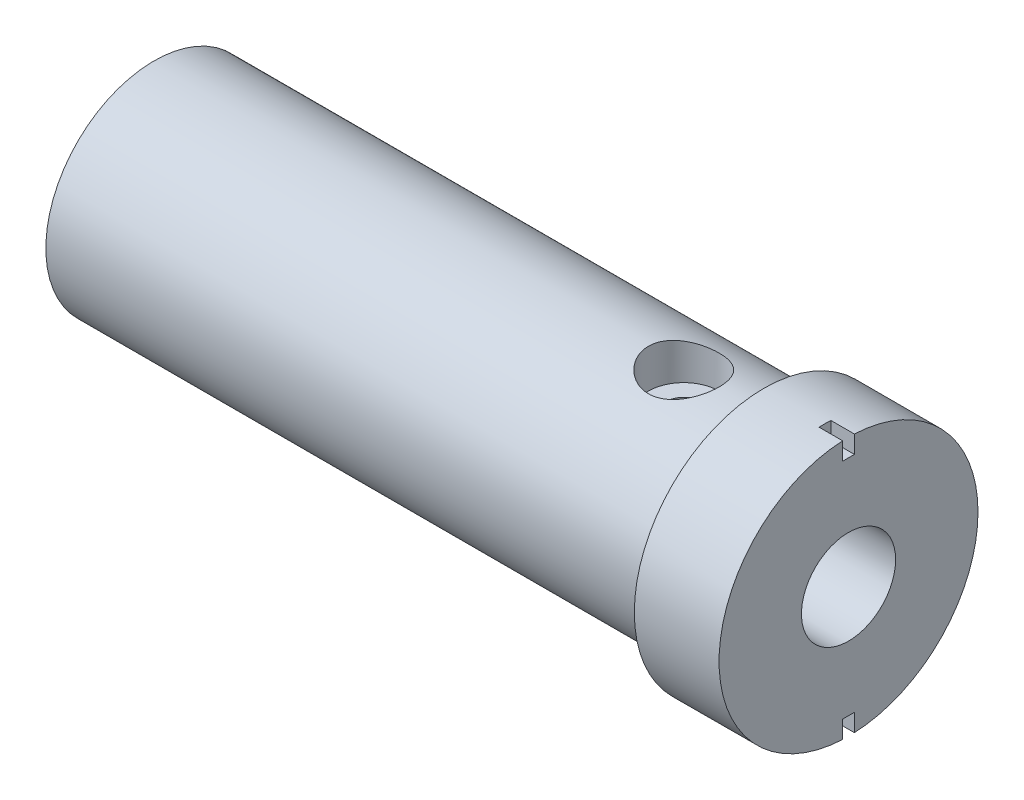
SolidWorks part; units mm, degrees
material "1060 Alloy"
ref_plane "Front Plane" through (0, 0, 0) normal (0, 0, 1) x (1, 0, 0)
ref_plane "Top Plane" through (0, 0, 0) normal (0, 1, 0) x (1, 0, 0)
ref_plane "Right Plane" through (0, 0, 0) normal (1, 0, 0) x (0, 0, -1)
ref_plane "Plane2" through (0, 3.1, 0) normal (0, 1, 0) x (1, 0, 0)
sketch "Sketch1" plane through (0, 0, 0) normal (0, 1, 0) x (1, 0, 0)
  line L0 (0, 0) -> (-90.15, 0) construction
  line L1 (0, 0) -> (0, 11)
  line L2 (0, 11) -> (-7.2, 11)
  line L3 (-7.2, 11) -> (-7.2, 9.2)
  line L4 (-7.2, 9.2) -> (-59, 9.2)
  line L5 (-59, 9.2) -> (-59, 0)
  line L6 (0, 0) -> (-59, 0)
  dimension "D1" = 7.2
  dimension "D2" = 59
  dimension "D3" = 11
  dimension "D4" = 9.2
revolve "Revolve1" add sketch "Sketch1" angle 360 about L0
sketch "Sketch2" plane through (0, 0, 0) normal (1, 0, 0) x (0, 0, -1)
  line L0 (-2.5278, 3.1) -> (2.5278, 3.1)
  line L1 (0.5, 10.9886) -> (0.5, 9.4886)
  line L2 (0.5, 9.4886) -> (-0.5, 9.4886)
  line L3 (-0.5, 9.4886) -> (-0.5, 10.9886)
  line L4 (0, 0) -> (4, 0) construction
  line L5 (-0.5, -9.4886) -> (-0.5, -10.9886)
  line L6 (0.5, -9.4886) -> (-0.5, -9.4886)
  line L7 (0.5, -10.9886) -> (0.5, -9.4886)
  circle A0 centre (0, 0) radius 4
  circle A1 centre (0, 0) radius 11 construction
  circle A2 centre (0, 0) radius 11
  circle M3 centre (0, 0) radius 11
  dimension "D1" = 8
  dimension "D2" = 3.1
  dimension "D3" = 0.5
  dimension "D4" = 1
  dimension "D5" = 1.5
extrude "Cut-Extrude1" cut sketch "Sketch2" against normal blind 20 contours L0 A0 | L0 A0 region at (0, 3.4637, 0) region at (0, -0.2284, 0)
sketch "Sketch3" plane through (0, 3.1, 0) normal (0, 1, 0) x (-1, 0, 0)
  line L0 (0, 0) -> (14, 0) construction
  circle A1 centre (14, 0) radius 1.475
  circle A2 centre (14, 0) radius 3
  point P5 (-14, 0)
  point P6 (-14, 0)
  point P7 (-14, 0)
  point P8 (14, 0)
  dimension "D2" = 2.95
  dimension "D3" = 6
  dimension "D1" = 14
extrude "Cut-Extrude3" cut sketch "Sketch3" along normal through all contours A1 region at (-14, 3.1, 0)
sketch "Sketch4" plane through (-59, 0, 0) normal (-1, 0, 0) x (0, 0, 1)
  line L0 (-3.0215, 3.1) -> (-3.0215, 8.6897) construction
  line L1 (3, 3.1) -> (-3, 3.1) construction
  line L2 (-3.0215, 8.6897) -> (-3, 8.6897) construction
  line L3 (-3, 8.6897) -> (-3, 3.1) construction
  circle A1 centre (0, 0) radius 9.2 construction
  dimension "D1" = 5.5897
extrude "Cut-Extrude4" cut sketch "Sketch3<4>" along normal through all from offset 2.8
sketch "Sketch3<4>" plane through (0, 3.1, 0) normal (0, 1, 0) x (-1, 0, 0) same geometry as "Sketch3"
extrude "Cut-Extrude5" cut sketch "Sketch2<6>" against normal blind 2 contours L3 L2 L1 M3 | L7 L6 L5 M3 region at (0, 10.2424, 0) region at (0, -10.2424, 0)
sketch "Sketch2<6>" plane through (0, 0, 0) normal (1, 0, 0) x (0, 0, -1) same geometry as "Sketch2"
